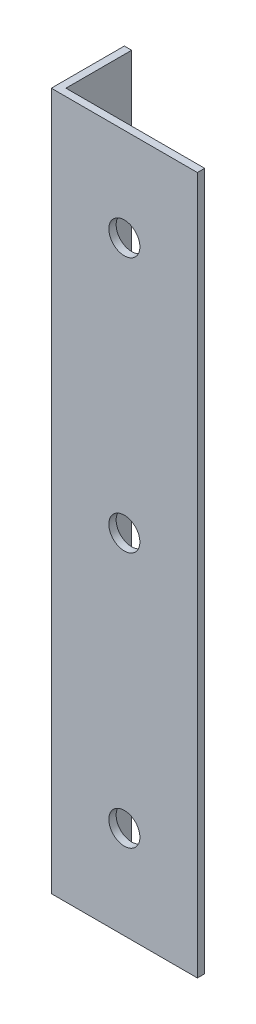
SolidWorks part; units mm, degrees
material "1060 Сплав"
ref_plane "Спереди" through (0, 0, 0) normal (0, 0, 1) x (1, 0, 0)
ref_plane "Сверху" through (0, 0, 0) normal (0, 1, 0) x (1, 0, 0)
ref_plane "Справа" through (0, 0, 0) normal (1, 0, 0) x (0, 0, -1)
sketch "Эскиз1" plane through (0, 0, 0) normal (0, 1, 0) x (1, 0, 0)
  line L0 (0, 0) -> (0, 20)
  line L1 (0, 20) -> (2, 20)
  line L2 (2, 20) -> (2, 2)
  line L3 (2, 2) -> (40, 2)
  line L4 (40, 2) -> (40, 0)
  line L5 (40, 0) -> (0, 0)
  dimension "D1" = 2
  dimension "D2" = 40
  dimension "D3" = 20
extrude "Бобышка-Вытянуть1" add sketch "Эскиз1" along normal blind 191
sketch "Эскиз2" plane through (0, 0, 0) normal (0, 0, 1) x (1, 0, 0)
  line L0 (20, 191) -> (20, 0) construction
  line L1 (0, 191) -> (40, 191) construction
  line L2 (0, 0) -> (40, 0) construction
  line L3 (40, 95.5) -> (0, 95.5) construction
  line L4 (40, 191) -> (40, 0) construction
  line L5 (0, 191) -> (0, 0) construction
  circle A1 centre (20, 165.5) radius 4.25
  circle A2 centre (20, 95.5) radius 4.25
  circle A3 centre (20, 25.5) radius 4.25
  dimension "D1" = 70
  dimension "D2" = 70
  dimension "D4" = 8.5
extrude "Вырез-Вытянуть1" cut sketch "Эскиз2" against normal through all
